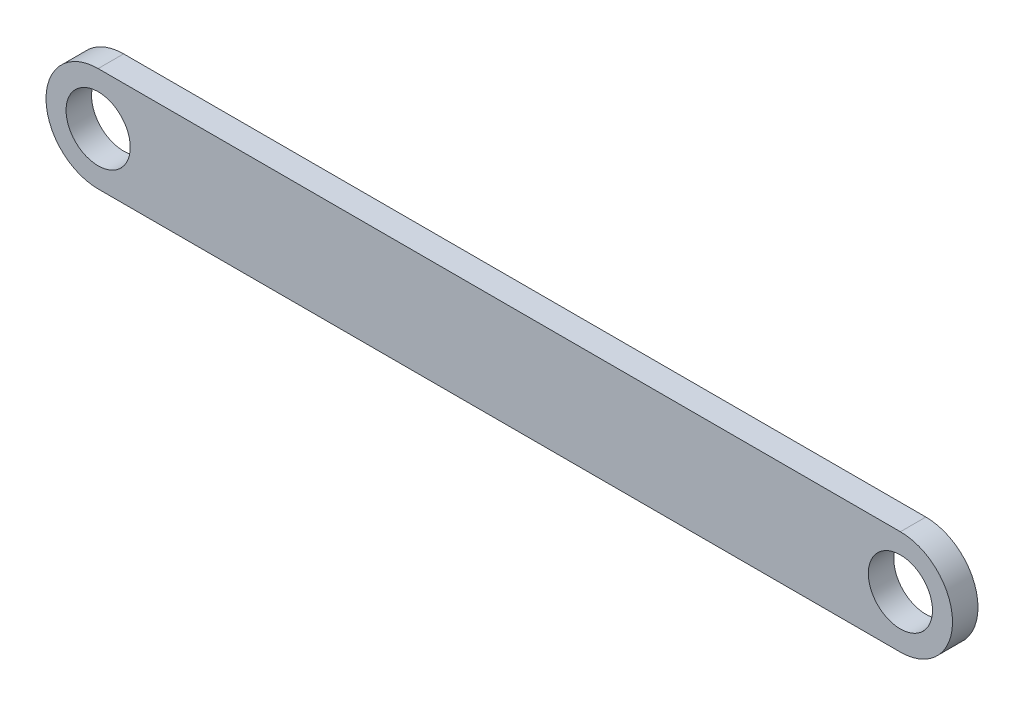
SolidWorks part; units mm, degrees
material "6061 Alloy"
ref_plane "Front Plane" through (0, 0, 0) normal (0, 0, 1) x (1, 0, 0)
ref_plane "Top Plane" through (0, 0, 0) normal (0, 1, 0) x (1, 0, 0)
ref_plane "Right Plane" through (0, 0, 0) normal (1, 0, 0) x (0, 0, -1)
sketch "Sketch1" plane through (0, 0, 0) normal (0, 0, 1) x (1, 0, 0)
  line L0 (-50, 0) -> (50, 0) construction
  line L1 (-50, 6.5) -> (50, 6.5)
  line L2 (-50, -6.5) -> (50, -6.5)
  arc A0 (-50, 6.5) -> (-50, -6.5) centre (-50, 0) ccw
  arc A1 (50, -6.5) -> (50, 6.5) centre (50, 0) ccw
  circle A2 centre (-50, 0) radius 4
  circle A3 centre (50, 0) radius 4
  point P2 (0, 0)
  dimension "D1" = 8
  dimension "D2" = 100
  dimension "D3" = 13
extrude "Boss-Extrude1" add sketch "Sketch1" along normal blind 3.175
